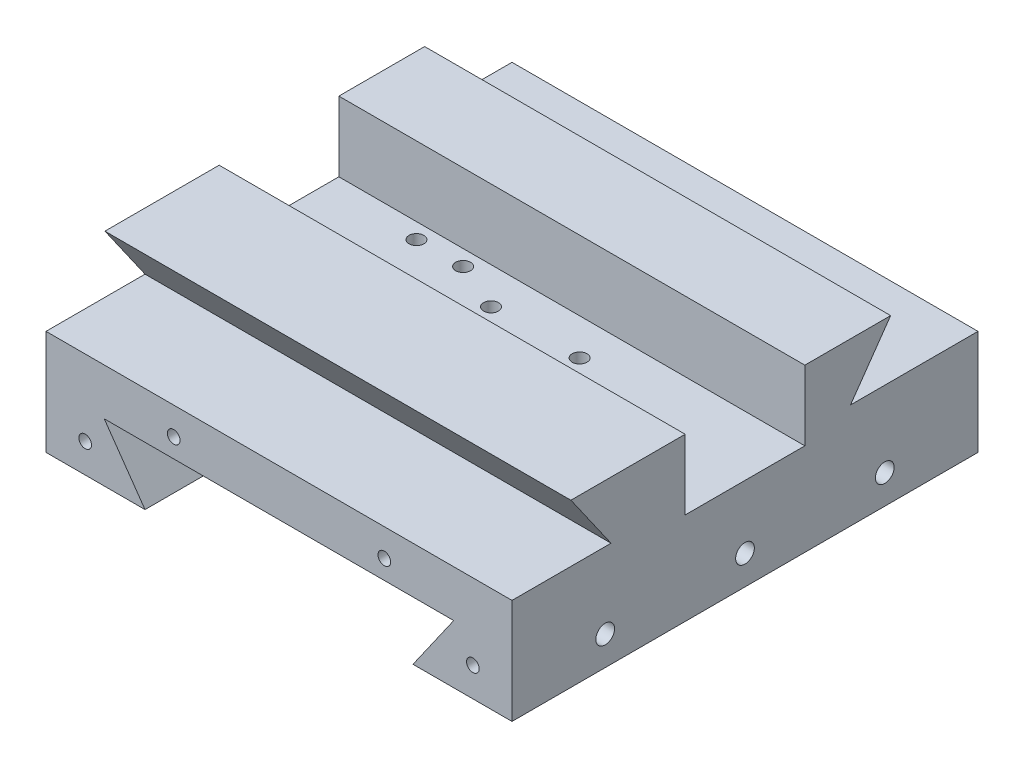
SolidWorks part; units mm, degrees
material "Ductile Iron"
ref_plane "Front Plane" through (0, 0, 0) normal (0, 0, 1) x (1, 0, 0)
ref_plane "Top Plane" through (0, 0, 0) normal (0, 1, 0) x (1, 0, 0)
ref_plane "Right Plane" through (0, 0, 0) normal (1, 0, 0) x (0, 0, -1)
sketch "Sketch10" plane through (0, 0, 0) normal (0, 0, 1) x (1, 0, 0)
  line B0 (-63.5, -15.875) -> (63.5, -15.875)
  line B1 (63.5, 0) -> (36.5092, 0)
  line B2 (36.5092, 0) -> (47.625, 15.875)
  line B3 (47.625, 15.875) -> (16.0563, 15.875)
  line B4 (-39.8731, 15.875) -> (-28.7573, 0)
  line B5 (-28.7573, 0) -> (-63.5, 0)
  line B6 (-63.5, 0) -> (-63.5, -15.875)
  line B7 (-36.5092, 0) -> (-47.625, 15.875)
  line B8 (-47.625, 15.875) -> (-39.8731, 15.875)
  line B9 (-16.0563, 15.875) -> (-16.0563, -3.175)
  line B10 (-16.0563, -3.175) -> (16.0563, -3.175)
  line B11 (16.0563, -3.175) -> (16.0563, 15.875)
  line B12 (-16.0563, 15.875) -> (-39.8731, 15.875)
  line B13 (-63.5, 0) -> (-63.5, 31.75)
  line B14 (-63.5, 31.75) -> (63.5, 31.75)
  line B15 (63.5, 31.75) -> (63.5, 0)
  line B16 (-16.0563, 15.875) -> (16.0563, 15.875)
  line B17 (0, 31.75) -> (0, -15.875) construction
  line B18 (-36.5092, 0) -> (36.5092, 0) construction
  line B19 (-28.702, 21.082) -> (28.702, 21.082) construction
  line B20 (-25.4, -8.001) -> (25.4, -8.001) construction
  line B21 (-25.4, -8.001) -> (-25.4, 7.9375) construction
  line B22 (25.4, -8.001) -> (25.4, 7.9375) construction
  line B23 (-52.832, 7.9375) -> (52.832, 7.9375) construction
  circle B24 centre (0, 6.35) radius 18.669 construction
  line B25 (39.8731, 15.875) -> (28.7573, 0)
  line B26 (28.7573, 0) -> (36.5092, 0)
sketch_block_instance "dovetail pair-1"
sketch_block "dovetail pair" parameters "D8"=37.338, "D1"=55, "D2"=127, "D3"=6.35, "D4"=15.875, "D5"=31.75, "D6"=95.25, "D7"=19.05, "D9"=55, "D10"=31.75, "D11"=50.8, "D12"=23.876, "D13"=7.874, "D14"=10.668, "D15"=34.798, "D16"=21.082, "D17"=7.9375
sketch "Sketch11"
sketch_block_instance "dovetail pair-3"
sketch "female-dovetail-profile" plane through (0, 0, 0) normal (0, 0, 1) x (1, 0, 0)
  line L0 (-47.625, 15.875) -> (-39.8731, 15.875) construction
  line L1 (-16.0563, 15.875) -> (-39.8731, 15.875) construction
  line L2 (-16.0563, 15.875) -> (16.0563, 15.875) construction
  line L3 (47.625, 15.875) -> (16.0563, 15.875) construction
  line L4 (-47.625, 15.875) -> (-39.8731, 15.875)
  line L5 (-16.0563, 15.875) -> (-39.8731, 15.875)
  line L6 (-16.0563, 15.875) -> (16.0563, 15.875)
  line L7 (47.625, 15.875) -> (16.0563, 15.875)
  line L8 (-36.5092, 0) -> (-47.625, 15.875) construction
  line L9 (-63.5, 0) -> (-63.5, 31.75) construction
  line L10 (63.5, 31.75) -> (63.5, 0) construction
  line L11 (63.5, 0) -> (36.5092, 0) construction
  line L12 (36.5092, 0) -> (47.625, 15.875) construction
  line L13 (-36.5092, 0) -> (-47.625, 15.875)
  line L14 (-63.5, 0) -> (-63.5, 31.75)
  line L15 (63.5, 31.75) -> (63.5, 0)
  line L16 (63.5, 0) -> (36.5092, 0)
  line L17 (36.5092, 0) -> (47.625, 15.875)
  line L18 (-36.5092, 0) -> (-63.5, 0)
  line L20 (63.5, 31.75) -> (63.5, 44.45)
  line L21 (63.5, 44.45) -> (-63.5, 44.45)
  line L22 (-63.5, 44.45) -> (-63.5, 31.75)
  dimension "D1" = 44.45
extrude "x-carriage-extrude" add sketch "female-dovetail-profile" along normal mid plane 127
sketch "male-dovetail-shoulder-profile" plane through (0, 0, 0) normal (1, 0, 0) x (0, 0, -1)
  line L0 (39.8731, 44.45) -> (28.7573, 28.575) construction
  line L1 (-39.8731, 44.45) -> (-28.7573, 28.575) construction
  line L2 (36.5092, 28.575) -> (47.625, 44.45) construction
  line L3 (63.5, 28.575) -> (36.5092, 28.575) construction
  line L4 (-36.5092, 28.575) -> (-47.625, 44.45) construction
  line L5 (-39.8731, 44.45) -> (-28.7573, 28.575) construction
  line L6 (36.5092, 28.575) -> (47.625, 44.45) construction
  line L7 (63.5, 28.575) -> (36.5092, 28.575)
  line L8 (-16.0563, 44.45) -> (-16.0563, 25.4) construction
  line L9 (-16.0563, 25.4) -> (16.0563, 25.4) construction
  line L10 (16.0563, 25.4) -> (16.0563, 44.45) construction
  line L11 (47.625, 44.45) -> (16.0563, 44.45) construction
  line L12 (-47.4471, 44.196) -> (-36.5092, 28.575)
  line L13 (-16.0563, 44.45) -> (-39.8731, 44.45) construction
  line L14 (-16.0563, 44.45) -> (-16.0563, 25.4) construction
  line L15 (-16.0563, 25.4) -> (16.0563, 25.4) construction
  line L16 (16.0563, 25.4) -> (16.0563, 44.45) construction
  line L17 (47.625, 44.45) -> (16.0563, 44.45) construction
  line L18 (-36.5092, 28.575) -> (-63.5, 28.575)
  line L19 (-16.0563, 44.45) -> (-39.8731, 44.45) construction
  line L20 (-47.4471, 44.196) -> (-16.3103, 44.196)
  line L21 (-16.3103, 44.196) -> (-16.3103, 25.146)
  line L22 (-16.3103, 25.146) -> (16.3103, 25.146)
  line L23 (16.3103, 25.146) -> (16.3103, 44.196)
  line L24 (16.3103, 44.196) -> (39.6952, 44.196)
  line L25 (39.6952, 44.196) -> (28.7573, 28.575)
  line L26 (-63.5, 28.575) -> (-63.5, 44.45)
  line L27 (-63.5, 44.45) -> (63.5, 44.45)
  line L28 (63.5, 44.45) -> (63.5, 28.575)
  line L29 (0, 60.325) -> (0, 12.7) construction
  line L30 (28.7573, 28.575) -> (36.5092, 28.575) construction
  line L31 (28.7573, 28.575) -> (36.5092, 28.575)
  point P16 (0, 25.146)
  dimension "D2" = 0.254
  dimension "D3" = 0.254
  dimension "D1" = 0.254
extrude "y-guide-cut-extrude" cut sketch "male-dovetail-shoulder-profile" against normal mid plane 127
hole_wizard "#8-32 Tapped Hole1" positions "Sketch4" profile "Sketch5" tap size "#8-32" standard "ANSI Inch"
sketch "Sketch4" plane through (0, -15.875, 63.5) normal (0, 0, 1) x (1, 0, 0)
  point P32 (-52.832, 23.8125)
  point P34 (-28.702, 36.957)
  point P36 (28.702, 36.957)
  point P38 (52.832, 23.8125)
cosmetic thread "Hole Thread12" parameters "D1"=8.382, "D2"=4.1656
sketch "Sketch5" plane through (-52.832, 7.9375, 63.5) normal (1, 0, 0) x (0, -1, 0)
  line L0 (0, 0) -> (0, 13.3822)
  line L1 (0, 13.3822) -> (1.7272, 12.3444)
  line L2 (1.7272, 12.3444) -> (1.7272, 0)
  line L3 (1.7272, 0) -> (0, 0)
  line L4 (0, 13.3822) -> (-1.7272, 12.3444) construction
  line L5 (0, -6.35) -> (0, 107.95) construction
  dimension "Tap Drill Dia." = 3.4544
  dimension "Tap Drill Depth" = 12.3444
  dimension "Drill Angle" = 118
cosmetic thread "Hole Thread20" parameters "D1"=8.382, "D2"=4.1656
cosmetic thread "Hole Thread21" parameters "D1"=8.382, "D2"=4.1656
cosmetic thread "Hole Thread22" parameters "D1"=8.382, "D2"=4.1656
hole_wizard "#8-32 Tapped Hole2" positions "Sketch6" profile "Sketch7" tap size "#8-32" standard "ANSI Inch"
sketch "Sketch6" plane through (0, -15.875, -63.5) normal (0, 0, -1) x (-1, 0, 0)
  point P8 (-52.832, 23.8125)
  point P10 (-28.702, 36.957)
  point P12 (28.702, 36.957)
  point P14 (52.832, 23.8125)
cosmetic thread "Hole Thread15" parameters "D1"=8.382, "D2"=4.1656
sketch "Sketch7" plane through (52.832, 7.9375, -63.5) normal (1, 0, 0) x (0, 1, 0)
  line L0 (0, 0) -> (0, 13.4838)
  line L1 (0, 13.4838) -> (1.7272, 12.446)
  line L2 (1.7272, 12.446) -> (1.7272, 0)
  line L5 (1.7272, 0) -> (0, 0)
  line L10 (0, 13.4838) -> (-1.7272, 12.446) construction
  line L11 (0, -6.35) -> (0, 107.95) construction
  dimension "Tap Drill Dia." = 3.4544
  dimension "Tap Drill Depth" = 12.446
  dimension "Drill Angle" = 118
cosmetic thread "Hole Thread23" parameters "D1"=8.382, "D2"=4.1656
cosmetic thread "Hole Thread24" parameters "D1"=8.382, "D2"=4.1656
cosmetic thread "Hole Thread25" parameters "D1"=8.382, "D2"=4.1656
hole_wizard "gib screw 1/4-20 Tapped Hole1" positions "Sketch9" profile "Sketch8" tap size "1/4-20" standard "ANSI Inch" end condition up to next
sketch "Sketch9" plane through (0, 0, 0) normal (1, 0, 0) x (0, 0, -1)
  line L2 (0, 15.875) -> (0, 0) construction
  line L4 (63.5, 7.9375) -> (-63.5, 7.9375) construction
  line L7 (-38.1, 7.9375) -> (0, 7.9375) construction
  line L8 (63.5, 0) -> (63.5, 28.575) construction
  line L9 (-63.5, 15.875) -> (63.5, 15.875) construction
  line L10 (-63.5, 15.875) -> (63.5, 15.875)
  point P0 (-38.1, 7.9375)
  point P16 (0, 7.9375)
  point P22 (0, 7.9375)
  point P23 (38.1, 7.9375)
  dimension "D1" = 38.1
  dimension "D2" = 3
sketch "Sketch8" plane through (0, 7.9375, 38.1) normal (0, 1, 0) x (0, 0, 1)
  line L0 (0, 0) -> (0, 63.5)
  line L1 (0, 63.5) -> (2.5527, 63.5)
  line L2 (2.5527, 63.5) -> (2.5527, 0)
  line L5 (2.5527, 0) -> (0, 0)
  line L11 (0, -6.35) -> (0, 107.95) construction
  dimension "Thru Tap Drill Dia." = 5.1054
  dimension "Thru Tap Drill Depth" = 63.5
cosmetic thread "Hole Thread36" parameters "D1"=23.2203, "D2"=6.35
cosmetic thread "Hole Thread37" parameters "D1"=23.2203, "D2"=6.35
cosmetic thread "Hole Thread38" parameters "D1"=23.2203, "D2"=6.35
hole_wizard "#10-32 Tapped Hole1" positions "Sketch13" profile "Sketch12" tap size "#10-32" standard "ANSI Inch" end condition up to next
sketch "Sketch13" plane through (0, 25.146, 0) normal (0, 1, 0) x (1, 0, 0)
  line L1 (-12.065, -6.35) -> (12.065, -6.35) construction
  line L2 (-12.065, -6.35) -> (-12.065, 6.35) construction
  line L3 (-12.065, 6.35) -> (12.065, 6.35) construction
  line L4 (12.065, -6.35) -> (12.065, 6.35) construction
  line L6 (-38.1, -12.065) -> (-25.4, -12.065) construction
  line L7 (-38.1, -12.065) -> (-38.1, 12.065) construction
  line L8 (-38.1, 12.065) -> (-25.4, 12.065) construction
  line L9 (-25.4, -12.065) -> (-25.4, 12.065) construction
  line L10 (0, 16.3103) -> (0, -16.3103) construction
  line L12 (-63.5, -16.3103) -> (63.5, -16.3103) construction
  line L13 (-63.5, 0) -> (63.5, 0) construction
  line L14 (-63.5, -16.3103) -> (-63.5, 16.3103) construction
  line L15 (63.5, -16.3103) -> (63.5, 16.3103) construction
  line L16 (-63.5, 16.3103) -> (63.5, 16.3103) construction
  point P0 (-38.1, 12.065)
  point P2 (-38.1, -12.065)
  point P4 (-12.065, 6.35)
  point P6 (-25.4, 12.065)
  point P8 (-25.4, -12.065)
  point P10 (12.065, 6.35)
  point P12 (12.065, -6.35)
  point P14 (-12.065, -6.35)
  point P155 (0, 0)
  point P157 (0, -6.35)
  point P158 (12.065, 0)
  point P159 (-25.4, 0)
  dimension "D1" = 24.13
  dimension "D2" = 24.13
  dimension "D3" = 12.7
  dimension "D4" = 12.7
  dimension "D5" = 38.1
sketch "Sketch12" plane through (-38.1, 25.146, -12.065) normal (1, 0, 0) x (0, 0, 1)
  line L0 (0, 0) -> (0, 9.271)
  line L1 (0, 9.271) -> (2.0193, 9.271)
  line L2 (2.0193, 9.271) -> (2.0193, 0)
  line L5 (2.0193, 0) -> (0, 0)
  line L11 (0, -6.35) -> (0, 107.95) construction
  dimension "Thru Tap Drill Dia." = 4.0386
  dimension "Thru Tap Drill Depth" = 9.271
cosmetic thread "Hole Thread28" parameters "D2"=4.826
cosmetic thread "Hole Thread29" parameters "D2"=4.826
cosmetic thread "Hole Thread30" parameters "D2"=4.826
cosmetic thread "Hole Thread31" parameters "D2"=4.826
cosmetic thread "Hole Thread32" parameters "D2"=4.826
cosmetic thread "Hole Thread33" parameters "D2"=4.826
cosmetic thread "Hole Thread34" parameters "D2"=4.826
cosmetic thread "Hole Thread35" parameters "D2"=4.826
equation "\"dovetail-angle\" = 55"
equation "\"dovetail-stock-width\" = 5"
equation "\"dovetail-stock-height\" = 1.25"
equation "\"dovetail-depth\" = 0.5 * \"dovetail-stock-height\""
equation "\"dovetail-throat-width\" = \"dovetail-stock-width\" - (2 * \"dovetail-depth\")"
equation "\"delta-x\" = 6"
equation "\"delta-y\" = 3"
equation "\"delta-z\"= 2.5"
equation "\"gib-thickness\" = 0.25"
equation "\"x-slide-length\" = \"dovetail-stock-width\" + \"delta-x\""
equation "\"y-slide-length\" = \"dovetail-stock-width\" + \"delta-y\""
equation "\"dog-point-diam\" = .149"
equation "\"D1@female-dovetail-profile\"=\"dovetail-double-height\""
equation "\"D1@x-carriage-extrude\"=\"dovetail-stock-width\""
equation "\"dog-point-length\" = .067"
equation "\"dovetail-double-height\" = 2 * \"dovetail-depth\" + 0.5"
equation "\"D2@male-dovetail-shoulder-profile\"=\"acme_nut_clearance\""
equation "\"D3@male-dovetail-shoulder-profile\"=\"dovetail_male_clearance\""
equation "\"acme-major-diam\" = .5"
equation "\"acme-pitch-diam\" = 0.45"
equation "\"acme-minor-diam\" = 0.4"
equation "\"acme-nut-od\" = 1.47"
equation "\"acme-nut-length\" = 1"
equation "\"acme-nut-trim-height\" = .75"
equation "\"screw-bearing-od\" = 0.5"
equation "\"screw-bearing-length\" = .375"
equation "\"screw-bearing-id\" = .375"
equation "\"end-plate-thickness\" = \"screw-bearing-length\""
equation "\"screw-add-length\" = 2 * \"end-plate-thickness\" + 1 + 0.5"
equation "\"x-screw-length\" = \"x-slide-length\" + \"screw-add-length\""
equation "\"y-screw-length\" = \"y-slide-length\" + \"screw-add-length\""
equation "\"acme-nut-mount-hole-space-horz\" = 0.95"
equation "\"acme-nut-mount-hole-space-vert\" = 0.5 * \"acme-nut-length\""
equation "\"D2@dovetail pair\"=\"dovetail-stock-width\""
equation "\"D1@dovetail pair\"=\"dovetail-angle\""
equation "\"D3@dovetail pair\"=\"gib-thickness\""
equation "\"D4@dovetail pair\"=\"dovetail-depth\""
equation "\"D5@dovetail pair\"=\"dovetail-stock-height\""
equation "\"D6@dovetail pair\"=\"dovetail-throat-width\""
equation "\"D10@dovetail pair\"=\"dovetail-stock-height\""
equation "\"D7@dovetail pair\"=\"acme-nut-trim-height\""
equation "\"D8@dovetail pair\"=\"acme-nut-od\""
equation "\"D9@dovetail pair\"=\"dovetail-angle\""
equation "\"D17@dovetail pair\"=\"dovetail-depth\"/2"
equation "\"acme-nut-trim-width\" = 1.25"
equation "\"vise-hole-center-dist\" = 6.75"
equation "\"wiper_plate_clearance\" = .03"
equation "\"dial-width\" = 0.5"
equation "\"quarter-twenty-free-fit\" = .2667"
equation "\"acme_nut_clearance\" = .01"
equation "\"dovetail_male_clearance\" = .01"
equation "\"D1@y-guide-cut-extrude\"=\"dovetail-stock-width\""
equation "\"D1@male-dovetail-shoulder-profile\"=\"acme_nut_clearance\""
equation "\"D1@Sketch13\"=\"acme-nut-mount-hole-space-horz\""
equation "\"D2@Sketch13\"=\"acme-nut-mount-hole-space-horz\""
equation "\"D3@Sketch13\"=\"acme-nut-mount-hole-space-vert\""
equation "\"D4@Sketch13\"=\"acme-nut-mount-hole-space-vert\""
